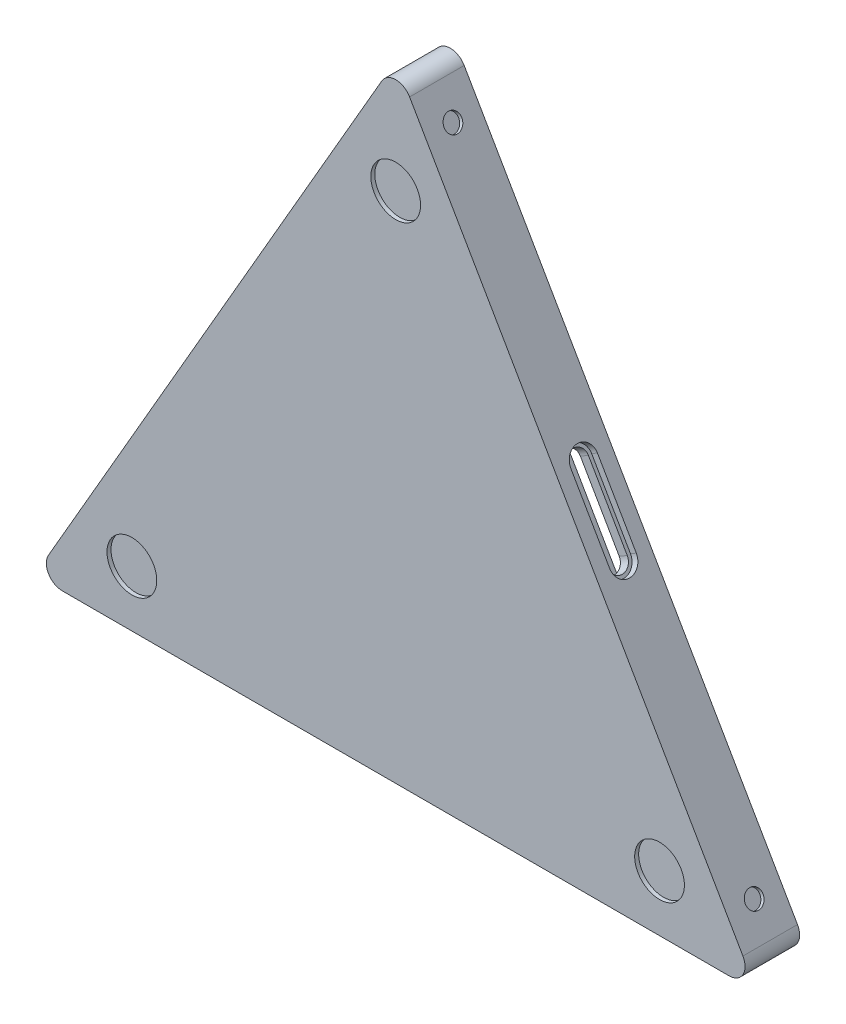
SolidWorks part; units mm, degrees
ref_plane "Plan de face" through (0, 0, 0) normal (0, 0, 1) x (1, 0, 0)
ref_plane "Plan de dessus" through (0, 0, 0) normal (0, 1, 0) x (1, 0, 0)
ref_plane "Plan de droite" through (0, 0, 0) normal (1, 0, 0) x (0, 0, -1)
sketch "Esquisse1" plane through (0, 0, 0) normal (0, 0, 1) x (1, 0, 0)
  line L0 (-169.7182, -51.3779) -> (-57.2182, 143.4778)
  line L1 (-57.2182, 143.4778) -> (55.2818, -51.3779)
  line L2 (55.2818, -51.3779) -> (-169.7182, -51.3779)
  line L3 (46.6215, -46.3779) -> (-161.058, -46.3779)
  line L4 (-161.058, -46.3779) -> (-57.2182, 133.4778)
  line L5 (-57.2182, 133.4778) -> (46.6215, -46.3779)
  dimension "D1" = 225
  dimension "D2" = 5
extrude "Boss.-Extru.1" add sketch "Esquisse1" along normal blind 15
sketch "Esquisse2" plane through (0, 0, 15) normal (0, 0, 1) x (1, 0, 0)
  line L0 (-57.2182, 143.4778) -> (-169.7182, -51.3779) construction
  line L1 (-169.7182, -51.3779) -> (55.2818, -51.3779) construction
  line L2 (55.2818, -51.3779) -> (-57.2182, 143.4778) construction
  line L3 (-57.2182, 143.4778) -> (-169.7182, -51.3779)
  line L4 (-169.7182, -51.3779) -> (55.2818, -51.3779)
  line L5 (55.2818, -51.3779) -> (-57.2182, 143.4778)
extrude "Boss.-Extru.2" add sketch "Esquisse2" along normal blind 2
sketch "Esquisse3" plane through (0, 0, 15) normal (0, 0, -1) x (-1, 0, 0)
  line L0 (53.949, 117.8154) -> (-28.5164, -25.019)
  line L1 (-46.6215, -46.3779) -> (57.2182, 133.4778) construction
  line L2 (53.949, 117.8154) -> (55.1614, 117.1154)
  line L3 (55.1614, 117.1154) -> (-27.304, -25.719)
  line L4 (-27.304, -25.719) -> (-28.5164, -25.019)
  line L5 (57.2182, 133.4778) -> (57.2182, -131.0717) construction
  line L6 (161.058, -46.3779) -> (-46.6215, -46.3779) construction
  line L7 (183.4656, -59.0638) -> (-91.5534, 99.7185) construction
  line L8 (-55.2818, -51.3779) -> (57.2182, 143.4778) construction
  line L25 (-46.6215, -46.3779) -> (181.6985, 85.4427) construction
  line L26 (57.2182, 143.4778) -> (169.7182, -51.3779) construction
  line L55 (149.0198, -35.5271) -> (147.8073, -36.2271)
  line L56 (149.0198, -35.5271) -> (66.5543, 107.3072)
  line L57 (65.3419, 106.6072) -> (66.5543, 107.3072)
  line L58 (147.8073, -36.2271) -> (65.3419, 106.6072)
  line L59 (-31.4228, -41.3779) -> (-31.4228, -39.9779)
  line L60 (-31.4228, -41.3779) -> (133.508, -41.3779)
  line L61 (133.508, -39.9779) -> (133.508, -41.3779)
  line L62 (-31.4228, -39.9779) -> (133.508, -39.9779)
  line L63 (57.2182, 133.4778) -> (161.058, -46.3779) construction
  line L64 (161.058, -46.3779) -> (-46.6215, -46.3779) construction
  dimension "D1" = 28
  dimension "D2" = 16
  dimension "D3" = 1.4
  dimension "D4" = 5
  dimension "D5" = 164.9309
  dimension "D6" = 1.4
  dimension "D7" = 5
  dimension "D8" = 5
  dimension "D9" = 5
  dimension "D10" = 1.4
extrude "Boss.-Extru.3" add sketch "Esquisse3" along normal blind 11
sketch "Esquisse4" plane through (19.214, 11.0932, 0) normal (0.866, 0.5, 0) x (0, 0, -1)
  line L0 (0, 40.3645) -> (-17, 40.3645) construction
  line L1 (-12.65, 52.4645) -> (-4.35, 28.2645) construction
  line L3 (-12.65, 52.4645) -> (-12.65, 28.2645)
  line L5 (-4.35, 52.4645) -> (-4.35, 28.2645)
  line L6 (-4.35, 52.4645) -> (-12.65, 28.2645) construction
  arc A0 (-4.35, 52.4645) -> (-12.65, 52.4645) centre (-8.5, 52.4645) ccw
  arc A1 (-12.65, 28.2645) -> (-4.35, 28.2645) centre (-8.5, 28.2645) ccw
  point P4 (-8.5, 40.3645)
  point P6 (-8.5, 40.3645)
  point P8 (-8.5, 56.6145)
  point P11 (-8.5, 24.1145)
  dimension "D1" = 8.3
  dimension "D2" = 32.5
extrude "Enlèv. mat.-Extru.1" cut sketch "Esquisse4" against normal blind 2.1
sketch "Esquisse5" plane through (17.3954, 10.0432, 0) normal (0.866, 0.5, 0) x (0, 0, -1)
  line L4 (-11.65, 52.4645) -> (-11.65, 28.2645)
  line L5 (-5.35, 28.2645) -> (-5.35, 52.4645)
  line L6 (-11.65, 52.4645) -> (-11.65, 28.2645)
  line L7 (-5.35, 28.2645) -> (-5.35, 52.4645)
  arc A4 (-11.65, 28.2645) -> (-5.35, 28.2645) centre (-8.5, 28.2645) ccw
  arc A5 (-5.35, 52.4645) -> (-11.65, 52.4645) centre (-8.5, 52.4645) ccw
  arc A6 (-11.65, 28.2645) -> (-5.35, 28.2645) centre (-8.5, 28.2645) ccw
  arc A7 (-5.35, 52.4645) -> (-11.65, 52.4645) centre (-8.5, 52.4645) ccw
  dimension "D1" = 1
extrude "Enlèv. mat.-Extru.2" cut sketch "Esquisse5" against normal up to next
fillet "Congé1" radius 5 6 edges at (-161.058, -46.3779, 7.5) (46.6215, -46.3779, 7.5) (-57.2182, 133.4778, 7.5) (-57.2182, 143.4778, 8.5) (-169.7182, -51.3779, 8.5) (55.2818, -51.3779, 8.5)
ref_plane "Plan1" through (-8.4268, -14.5957, 0) normal (0.5, 0.866, 0) x (0.866, -0.5, 0)
mirror "Symétrie1" about plane through (-8.4268, -14.5957, 0) normal (0.5, 0.866, 0) of "Enlèv. mat.-Extru.2", "Enlèv. mat.-Extru.1"
sketch "Esquisse6" plane through (0, 0, 17) normal (0, 0, 1) x (1, 0, 0)
  line L0 (-57.2182, 138.4778) -> (-57.2182, -78.2575) construction
  line L1 (-1.8061, -18.4182) -> (-15.0476, -10.7732) construction
  arc A0 (-52.8881, 135.9778) -> (-61.5484, 135.9778) centre (-57.2182, 133.4778) ccw construction
  circle A1 centre (-57.2182, 108.4778) radius 7.75
  circle A2 centre (-139.4073, -33.8779) radius 7.75
  circle A3 centre (24.9709, -33.8779) radius 7.75
  dimension "D1" = 15.5
  dimension "D2" = 30
extrude "Enlèv. mat.-Extru.3" cut sketch "Esquisse6" against normal blind 1.24
sketch "Esquisse7" plane through (0, -51.3779, 0) normal (0, -1, 0) x (1, 0, 0)
  line L0 (-161.058, 8.5) -> (46.6215, 8.5) construction
  line L1 (-161.058, 17) -> (-161.058, 0) construction
  line L2 (46.6215, 0) -> (46.6215, 17) construction
  line L3 (-57.2182, 17) -> (-57.2182, 0) construction
  line L4 (-161.058, 17) -> (46.6215, 17) construction
  line L5 (-161.058, 0) -> (46.6215, 0) construction
  circle A0 centre (36.6215, 8.5) radius 2.75
  circle A1 centre (-151.058, 8.5) radius 2.75
  dimension "D1" = 5.5
  dimension "D2" = 10
  dimension "D3" = 10
extrude "Enlèv. mat.-Extru.4" cut sketch "Esquisse7" against normal blind 1.14
mirror "Symétrie2" about plane through (-8.4268, -14.5957, 0) normal (0.5, 0.866, 0) of "Enlèv. mat.-Extru.4"
ref_plane "Plan2" through (-20.1823, 34.9567, 0) normal (0.5, -0.866, 0) x (-0.866, -0.5, 0)
mirror "Symétrie3" about plane through (-20.1823, 34.9567, 0) normal (0.5, -0.866, 0) of "Enlèv. mat.-Extru.4"
fillet "Congé2" radius 5 3 edges at (-12.7163, 46.3982, 15) (-51.0426, -41.3779, 15) (-107.787, 35.8901, 15)
sketch "Esquisse9" plane through (0, 0, 0) normal (0, 0, -1) x (-1, 0, 0)
  line L6 (164.0891, -44.6279) -> (60.2493, 135.2278)
  line L7 (54.1871, 135.2278) -> (-49.6526, -44.6279)
  line L8 (-46.6215, -49.8779) -> (161.058, -49.8779)
  line L9 (164.0891, -44.6279) -> (60.2493, 135.2278)
  line L10 (54.1871, 135.2278) -> (-49.6526, -44.6279)
  line L11 (-46.6215, -49.8779) -> (161.058, -49.8779)
  arc A6 (60.2493, 135.2278) -> (54.1871, 135.2278) centre (57.2182, 133.4778) ccw
  arc A7 (-49.6526, -44.6279) -> (-46.6215, -49.8779) centre (-46.6215, -46.3779) ccw
  arc A8 (161.058, -49.8779) -> (164.0891, -44.6279) centre (161.058, -46.3779) ccw
  arc A9 (60.2493, 135.2278) -> (54.1871, 135.2278) centre (57.2182, 133.4778) ccw
  arc A10 (-49.6526, -44.6279) -> (-46.6215, -49.8779) centre (-46.6215, -46.3779) ccw
  arc A11 (161.058, -49.8779) -> (164.0891, -44.6279) centre (161.058, -46.3779) ccw
  dimension "D1" = 1.5
extrude "Enlèv. mat.-Extru.6" cut sketch "Esquisse9" against normal blind 2
sketch "Esquisse8" plane through (0, 0, 0) normal (0, 0, -1) x (-1, 0, 0)
  line L0 (15.5716, -10.4707) -> (1.2821, -18.7207) construction
  line L2 (-42.2914, -43.8779) -> (-50.9516, -48.8779) construction
  line L3 (13.0376, 39.0817) -> (27.327, 30.8317) construction
  circle A0 centre (-45.9149, -45.9699) radius 2.75
  arc A3 (-37.9613, -46.3779) -> (-42.2914, -38.8779) centre (-37.9613, -41.3779) ccw construction
  arc A4 (-50.9516, -43.8779) -> (-46.6215, -51.3779) centre (-46.6215, -46.3779) ccw construction
  circle A5 centre (57.2182, 132.6619) radius 2.75
  circle A6 centre (160.3514, -45.9699) radius 2.75
  dimension "D1" = 5.5
extrude "Enlèv. mat.-Extru.5" cut sketch "Esquisse8" against normal blind 4
sketch3d "Esquisse3D1"
  line L0 (46.6215, -49.6779, 2) -> (-161.058, -49.6779, 2)
  line L1 (-163.9159, -44.7279, 2) -> (-60.0761, 135.1278, 2)
  line L2 (-54.3603, 135.1278, 2) -> (49.4769, -44.7236, 2)
  line L3 (46.6215, -49.6779, 2) -> (-161.058, -49.6779, 2)
  line L4 (-163.9159, -44.7279, 2) -> (-60.0761, 135.1278, 2)
  line L5 (-54.3603, 135.1278, 2) -> (49.4769, -44.7236, 2)
  spline S0 degree 5 poles (1548.4548, -2641.0281, 2) (32.9665, -16.1267, 2) (49.518, -44.7947, 2) (49.3846, -44.5638, 2) (49.433, -44.6476, 2) (49.4986, -44.7612, 2) (49.5179, -44.7945, 2) (49.5368, -44.828, 2) (49.5922, -44.9291, 2) (49.6405, -45.0342, 2) (49.67, -45.1056, 2) (49.7384, -45.2863, 2) (49.796, -45.4703, 2) (49.8263, -45.5818, 2) (49.8771, -45.8069, 2) (49.9071, -46.0361, 2) (49.917, -46.1514, 2) (49.9265, -46.3826, 2) (49.916, -46.6136, 2) (49.9058, -46.7288, 2) (49.8753, -46.9579, 2) (49.8248, -47.1835, 2) (49.7946, -47.2952, 2) (49.7246, -47.5156, 2) (49.6356, -47.729, 2) (49.5864, -47.8336, 2) (49.4791, -48.0385, 2) (49.3543, -48.2331, 2) (49.2877, -48.3276, 2) (49.1464, -48.5106, 2) (48.9896, -48.6806, 2) (48.9075, -48.7621, 2) (48.7365, -48.9177, 2) (48.5525, -49.0576, 2) (48.4575, -49.1236, 2) (48.262, -49.247, 2) (48.0564, -49.3532, 2) (47.9514, -49.4017, 2) (47.7385, -49.4887, 2) (47.5189, -49.5557, 2) (47.4083, -49.5844, 2) (47.2225, -49.6252, 2) (47.0341, -49.6552, 2) (46.9587, -49.6649, 2) (43.0328, -50.0198, 2) (38.9402, -41.0784, 2) (40.3026, -332.192, 2) (52.5851, -1232.0136, 2) (80.1963, -3049.3767, 2) knots -0.066432 -0.066432 -0.066432 -0.066432 -0.066432 -0.066432 0.000723 0.000723 0.000723 0.000723 0.028555 0.028555 0.028555 0.084219 0.084219 0.084219 0.167714 0.167714 0.167714 0.25121 0.25121 0.25121 0.334705 0.334705 0.334705 0.4182 0.4182 0.4182 0.501696 0.501696 0.501696 0.585191 0.585191 0.585191 0.668686 0.668686 0.668686 0.752182 0.752182 0.752182 0.835677 0.835677 0.835677 0.918283 0.918283 0.918283 0.973057 0.973057 0.973057 3.764575 3.764575 3.764575 3.764575 3.764575 3.764575 only from (49.4769, -44.7236, 2) to (46.6215, -49.6779, 2)
  spline S1 degree 5 poles (-197.3487, -3049.3016, 2) (-167.1709, -1231.5924, 2) (-154.6961, -331.7924, 2) (-153.2975, -40.8874, 2) (-157.4372, -50.0325, 2) (-161.4038, -49.6643, 2) (-161.4804, -49.6542, 2) (-161.6711, -49.623, 2) (-161.8592, -49.5809, 2) (-161.9709, -49.5514, 2) (-162.1913, -49.4829, 2) (-162.4048, -49.3942, 2) (-162.5095, -49.3451, 2) (-162.7145, -49.2378, 2) (-162.9093, -49.1132, 2) (-163.004, -49.0468, 2) (-163.1872, -48.9058, 2) (-163.3573, -48.7492, 2) (-163.4389, -48.6673, 2) (-163.5948, -48.4964, 2) (-163.735, -48.3126, 2) (-163.8011, -48.2177, 2) (-163.9249, -48.0224, 2) (-164.031, -47.817, 2) (-164.0796, -47.712, 2) (-164.1674, -47.4982, 2) (-164.2362, -47.2774, 2) (-164.2657, -47.1656, 2) (-164.315, -46.9397, 2) (-164.3442, -46.7103, 2) (-164.3538, -46.5951, 2) (-164.3629, -46.3641, 2) (-164.3521, -46.1329, 2) (-164.3416, -46.0177, 2) (-164.3105, -45.7899, 2) (-164.2587, -45.5662, 2) (-164.2283, -45.456, 2) (-164.1707, -45.2747, 2) (-164.1025, -45.0966, 2) (-164.0732, -45.0265, 2) (-162.4176, -41.4491, 2) (-152.6279, -42.3755, 2) (-405.4196, 102.0008, 2) (-1190.8253, 541.2724, 2) (-2778.5007, 1426.0489, 2) knots -2.794474 -2.794474 -2.794474 -2.794474 -2.794474 -2.794474 0.027852 0.027852 0.027852 0.083556 0.083556 0.083556 0.167112 0.167112 0.167112 0.250667 0.250667 0.250667 0.334223 0.334223 0.334223 0.417779 0.417779 0.417779 0.501335 0.501335 0.501335 0.584891 0.584891 0.584891 0.668446 0.668446 0.668446 0.752002 0.752002 0.752002 0.835558 0.835558 0.835558 0.918224 0.918224 0.918224 0.973038 0.973038 0.973038 3.766572 3.766572 3.766572 3.766572 3.766572 3.766572 only from (-161.058, -49.6779, 2) to (-163.9159, -44.7279, 2)
  spline S2 degree 5 poles (-2639.6826, 1666.3654, 2) (-1080.5876, 731.3789, 2) (-307.5754, 270.6755, 2) (-56.3435, 124.0118, 2) (-62.1936, 132.1694, 2) (-59.8914, 135.4205, 2) (-59.8443, 135.4817, 2) (-59.722, 135.6313, 2) (-59.5915, 135.7732, 2) (-59.5101, 135.8551, 2) (-59.3406, 136.0117, 2) (-59.157, 136.1523, 2) (-59.0621, 136.2185, 2) (-58.8667, 136.3424, 2) (-58.6614, 136.4488, 2) (-58.5565, 136.4975, 2) (-58.3428, 136.5857, 2) (-58.1222, 136.6547, 2) (-58.0104, 136.6844, 2) (-57.7845, 136.734, 2) (-57.5552, 136.7636, 2) (-57.44, 136.7734, 2) (-57.209, 136.7829, 2) (-56.978, 136.7721, 2) (-56.8628, 136.7616, 2) (-56.6337, 136.7308, 2) (-56.4081, 136.6799, 2) (-56.2965, 136.6496, 2) (-56.0762, 136.5793, 2) (-55.863, 136.4899, 2) (-55.7584, 136.4406, 2) (-55.5537, 136.3331, 2) (-55.359, 136.2081, 2) (-55.2644, 136.1414, 2) (-55.0827, 136.0006, 2) (-54.9149, 135.8439, 2) (-54.8347, 135.7625, 2) (-54.7065, 135.6219, 2) (-54.5863, 135.4738, 2) (-54.5402, 135.4134, 2) (-52.2699, 132.1909, 2) (-57.9671, 124.1759, 2) (193.4623, 270.9118, 2) (966.5855, 731.4574, 2) (2526.6641, 1664.0315, 2) knots -2.794474 -2.794474 -2.794474 -2.794474 -2.794474 -2.794474 0.027852 0.027852 0.027852 0.083556 0.083556 0.083556 0.167112 0.167112 0.167112 0.250667 0.250667 0.250667 0.334223 0.334223 0.334223 0.417779 0.417779 0.417779 0.501335 0.501335 0.501335 0.584891 0.584891 0.584891 0.668446 0.668446 0.668446 0.752002 0.752002 0.752002 0.835558 0.835558 0.835558 0.918224 0.918224 0.918224 0.973038 0.973038 0.973038 3.766572 3.766572 3.766572 3.766572 3.766572 3.766572 only from (-60.0761, 135.1278, 2) to (-54.3603, 135.1278, 2)
  spline S3 degree 5 poles (49.4769, -44.7236, 2) (49.4774, -44.7244, 2) (49.4779, -44.7253, 2) (49.4784, -44.7262, 2) (49.4789, -44.727, 2) (49.4986, -44.7612, 2) (49.5179, -44.7945, 2) (49.5368, -44.828, 2) (49.5922, -44.9291, 2) (49.6405, -45.0342, 2) (49.67, -45.1056, 2) (49.7384, -45.2863, 2) (49.796, -45.4703, 2) (49.8263, -45.5818, 2) (49.8771, -45.8069, 2) (49.9071, -46.0361, 2) (49.917, -46.1514, 2) (49.9265, -46.3826, 2) (49.916, -46.6136, 2) (49.9058, -46.7288, 2) (49.8753, -46.9579, 2) (49.8248, -47.1835, 2) (49.7946, -47.2952, 2) (49.7246, -47.5156, 2) (49.6356, -47.729, 2) (49.5864, -47.8336, 2) (49.4791, -48.0385, 2) (49.3543, -48.2331, 2) (49.2877, -48.3276, 2) (49.1464, -48.5106, 2) (48.9896, -48.6806, 2) (48.9075, -48.7621, 2) (48.7365, -48.9177, 2) (48.5525, -49.0576, 2) (48.4575, -49.1236, 2) (48.262, -49.247, 2) (48.0564, -49.3532, 2) (47.9514, -49.4017, 2) (47.7385, -49.4887, 2) (47.5189, -49.5557, 2) (47.4083, -49.5844, 2) (47.2225, -49.6252, 2) (47.0341, -49.6552, 2) (46.9587, -49.6649, 2) (46.846, -49.6751, 2) (46.7332, -49.6776, 2) (46.696, -49.6779, 2) (46.6587, -49.6779, 2) (46.6215, -49.6779, 2) knots 0.000001 0.000001 0.000001 0.000001 0.000001 0.000001 0.000723 0.000723 0.000723 0.000723 0.028555 0.028555 0.028555 0.084219 0.084219 0.084219 0.167714 0.167714 0.167714 0.25121 0.25121 0.25121 0.334705 0.334705 0.334705 0.4182 0.4182 0.4182 0.501696 0.501696 0.501696 0.585191 0.585191 0.585191 0.668686 0.668686 0.668686 0.752182 0.752182 0.752182 0.835677 0.835677 0.835677 0.918283 0.918283 0.918283 0.973057 0.973057 0.973057 1 1 1 1 1 1
  spline S4 degree 5 poles (-161.058, -49.6779, 2) (-161.0964, -49.6779, 2) (-161.1349, -49.6779, 2) (-161.1733, -49.6776, 2) (-161.2886, -49.6749, 2) (-161.4038, -49.6643, 2) (-161.4804, -49.6542, 2) (-161.6711, -49.623, 2) (-161.8592, -49.5809, 2) (-161.9709, -49.5514, 2) (-162.1913, -49.4829, 2) (-162.4048, -49.3942, 2) (-162.5095, -49.3451, 2) (-162.7145, -49.2378, 2) (-162.9093, -49.1132, 2) (-163.004, -49.0468, 2) (-163.1872, -48.9058, 2) (-163.3573, -48.7492, 2) (-163.4389, -48.6673, 2) (-163.5948, -48.4964, 2) (-163.735, -48.3126, 2) (-163.8011, -48.2177, 2) (-163.9249, -48.0224, 2) (-164.031, -47.817, 2) (-164.0796, -47.712, 2) (-164.1674, -47.4982, 2) (-164.2362, -47.2774, 2) (-164.2657, -47.1656, 2) (-164.315, -46.9397, 2) (-164.3442, -46.7103, 2) (-164.3538, -46.5951, 2) (-164.3629, -46.3641, 2) (-164.3521, -46.1329, 2) (-164.3416, -46.0177, 2) (-164.3105, -45.7899, 2) (-164.2587, -45.5662, 2) (-164.2283, -45.456, 2) (-164.1707, -45.2747, 2) (-164.1025, -45.0966, 2) (-164.0732, -45.0265, 2) (-164.0257, -44.9237, 2) (-163.9714, -44.8248, 2) (-163.9531, -44.7924, 2) (-163.9345, -44.7601, 2) (-163.9159, -44.7279, 2) knots 0 0 0 0 0 0 0.027852 0.027852 0.027852 0.083556 0.083556 0.083556 0.167112 0.167112 0.167112 0.250667 0.250667 0.250667 0.334223 0.334223 0.334223 0.417779 0.417779 0.417779 0.501335 0.501335 0.501335 0.584891 0.584891 0.584891 0.668446 0.668446 0.668446 0.752002 0.752002 0.752002 0.835558 0.835558 0.835558 0.918224 0.918224 0.918224 0.973038 0.973038 0.973038 1 1 1 1 1 1
  spline S5 degree 5 poles (-60.0761, 135.1278, 2) (-60.0569, 135.1611, 2) (-60.0377, 135.1944, 2) (-60.0182, 135.2275, 2) (-59.9582, 135.3261, 2) (-59.8914, 135.4205, 2) (-59.8443, 135.4817, 2) (-59.722, 135.6313, 2) (-59.5915, 135.7732, 2) (-59.5101, 135.8551, 2) (-59.3406, 136.0117, 2) (-59.157, 136.1523, 2) (-59.0621, 136.2185, 2) (-58.8667, 136.3424, 2) (-58.6614, 136.4488, 2) (-58.5565, 136.4975, 2) (-58.3428, 136.5857, 2) (-58.1222, 136.6547, 2) (-58.0104, 136.6844, 2) (-57.7845, 136.734, 2) (-57.5552, 136.7636, 2) (-57.44, 136.7734, 2) (-57.209, 136.7829, 2) (-56.978, 136.7721, 2) (-56.8628, 136.7616, 2) (-56.6337, 136.7308, 2) (-56.4081, 136.6799, 2) (-56.2965, 136.6496, 2) (-56.0762, 136.5793, 2) (-55.863, 136.4899, 2) (-55.7584, 136.4406, 2) (-55.5537, 136.3331, 2) (-55.359, 136.2081, 2) (-55.2644, 136.1414, 2) (-55.0827, 136.0006, 2) (-54.9149, 135.8439, 2) (-54.8347, 135.7625, 2) (-54.7065, 135.6219, 2) (-54.5863, 135.4738, 2) (-54.5402, 135.4134, 2) (-54.475, 135.3208, 2) (-54.4164, 135.2244, 2) (-54.3976, 135.1923, 2) (-54.379, 135.16, 2) (-54.3603, 135.1278, 2) knots 0 0 0 0 0 0 0.027852 0.027852 0.027852 0.083556 0.083556 0.083556 0.167112 0.167112 0.167112 0.250667 0.250667 0.250667 0.334223 0.334223 0.334223 0.417779 0.417779 0.417779 0.501335 0.501335 0.501335 0.584891 0.584891 0.584891 0.668446 0.668446 0.668446 0.752002 0.752002 0.752002 0.835558 0.835558 0.835558 0.918224 0.918224 0.918224 0.973038 0.973038 0.973038 1 1 1 1 1 1
  dimension "D1" = 0.2
